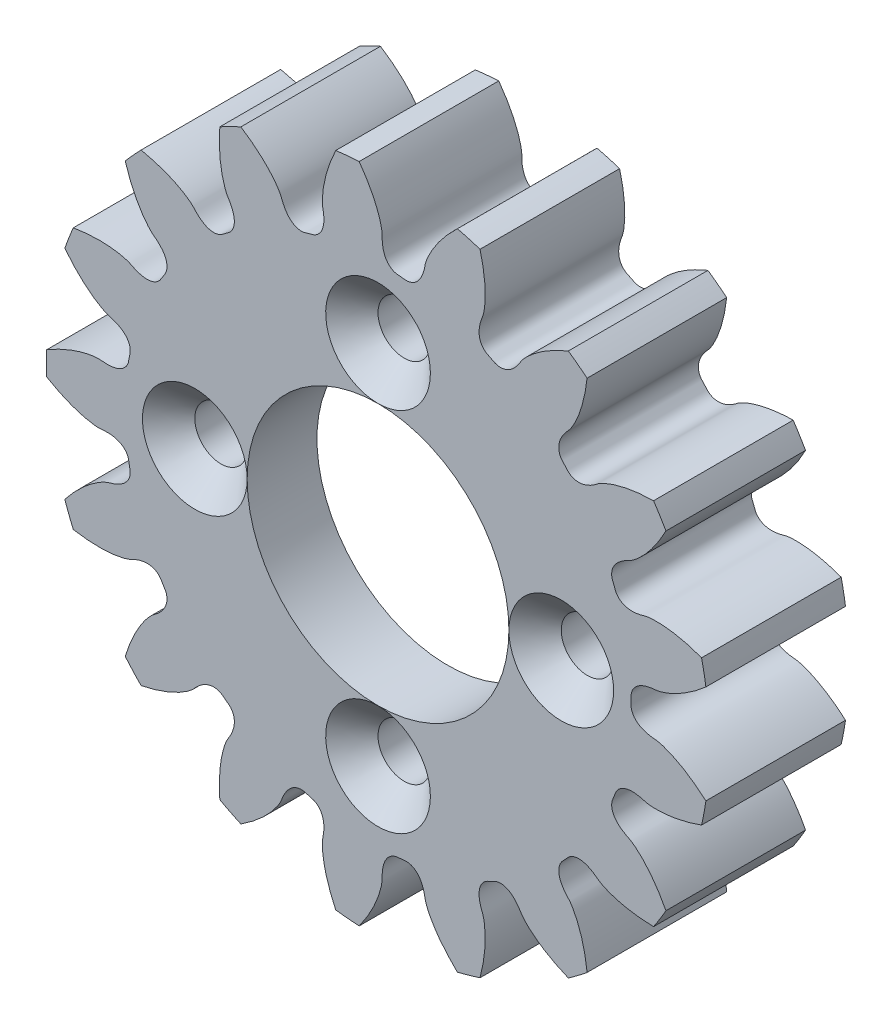
SolidWorks part; units mm, degrees
material "POM 乙缩醛共聚物"
ref_plane "前视基准面" through (0, 0, 0) normal (0, 0, 1) x (1, 0, 0)
ref_plane "上视基准面" through (0, 0, 0) normal (0, 1, 0) x (1, 0, 0)
ref_plane "右视基准面" through (0, 0, 0) normal (1, 0, 0) x (0, 0, -1)
ref_axis "基准轴1" through (0, 0, 55) along (0, 0, -1)
sketch "旋转草图小直齿轮" plane through (0, 0, 0) normal (1, 0, 0) x (0, 0, -1)
  line L0 (0, 0) -> (1, 0) construction
  line L1 (-3, 0) -> (-3, 19)
  line L2 (-3, 19) -> (3, 19)
  line L3 (3, 19) -> (3, 0)
  line L4 (3, 0) -> (-3, 0)
revolve "小直齿轮" add sketch "旋转草图小直齿轮" angle 360 about L0
sketch "齿草图小直齿轮" plane through (0, 0, 0) normal (0, 0, 1) x (1, 0, 0)
  arc A0 (18.8777, 2.9059) -> (18.8777, -2.9059) centre (0, 0) cw
  spline S0 degree 3 number of poles 107 (18.8777, -2.9059) -> (18.8777, 2.9059)
extrude "齿拉伸切除小直齿轮" cut sketch "齿草图小直齿轮" against normal blind 3 and the other way blind 3
pattern_circular "齿形小直齿轮" count 17 every 21.176 about axis through (0, 0, 55) along (0, 0, -1) of "齿拉伸切除小直齿轮"
sketch "孔旋转草图" plane through (0, 0, 0) normal (1, 0, 0) x (0, 0, -1)
  line L0 (0, 0) -> (1, 0) construction
  line L1 (-3, 0) -> (3, 0)
  line L2 (3, 0) -> (3, 5)
  line L3 (3, 5) -> (-3, 5)
  line L4 (-3, 5) -> (-3, 0)
  dimension "TaperSide1" = 5
  dimension "TaperSide2" = 5
revolve "孔旋转切除" cut sketch "孔旋转草图" angle 360 about L0
sketch "辅助草图小直齿轮" plane through (0, 0, 0) normal (0, 0, 1) x (1, 0, 0)
  circle A0 centre (0, 0) radius 17 construction
  circle A1 centre (0, 0) radius 15.9748 construction
  circle A2 centre (0, 0) radius 15.9784 construction
  circle A3 centre (0, 0) radius 19 construction
  circle A4 centre (0, 0) radius 14.5 construction
  dimension "PitchDiameter" = 34
  dimension "BaseDiameter" = 31.9495
  dimension "FormDiameter" = 31.9568
  dimension "MajorDiameter" = 38
  dimension "MinorDiameter" = 29
sketch "草图1" plane through (0, 0, 3) normal (0, 0, 1) x (1, 0, 0)
  circle A0 centre (0, 0) radius 7.5
  circle A1 centre (0, 0) radius 10.5 construction
  circle A2 centre (0, 10.5) radius 1.5
  circle A3 centre (10.5, 0) radius 1.5
  circle A4 centre (0, -10.5) radius 1.5
  circle A5 centre (-10.5, 0) radius 1.5
  point P15 (0, 0)
  dimension "D1" = 15
  dimension "D2" = 21
  dimension "D3" = 3
  dimension "D4" = 4
extrude "切除-拉伸1" cut sketch "草图1" against normal through all
sketch "草图2" plane through (0, 0, -3) normal (0, 0, 1) x (1, 0, 0)
  circle A0 centre (0, 0) radius 13.5
  arc A17 (10.905, -15.5589) -> (11.9807, -14.7466) centre (0, 0) ccw
  arc A18 (15.7892, -10.5689) -> (16.4987, -9.4229) centre (0, 0) ccw
  arc A19 (18.5409, -4.1515) -> (18.7886, -2.8266) centre (0, 0) ccw
  arc A20 (18.7886, 2.8266) -> (18.5409, 4.1515) centre (0, 0) ccw
  arc A21 (16.4987, 9.4229) -> (15.7892, 10.5689) centre (0, 0) ccw
  arc A22 (11.9807, 14.7466) -> (10.905, 15.5589) centre (0, 0) ccw
  arc A23 (5.8445, 18.0788) -> (4.5481, 18.4476) centre (0, 0) ccw
  arc A24 (-1.0809, 18.9692) -> (-2.4231, 18.8449) centre (0, 0) ccw
  arc A25 (-7.8604, 17.2978) -> (-9.067, 16.697) centre (0, 0) ccw
  arc A26 (-13.5783, 13.2902) -> (-14.4864, 12.2941) centre (0, 0) ccw
  arc A27 (-17.4624, 7.4877) -> (-17.9493, 6.2308) centre (0, 0) ccw
  arc A28 (-18.988, 0.6739) -> (-18.988, -0.6739) centre (0, 0) ccw
  arc A29 (-17.9493, -6.2308) -> (-17.4624, -7.4877) centre (0, 0) ccw
  arc A30 (-14.4864, -12.2941) -> (-13.5783, -13.2902) centre (0, 0) ccw
  arc A31 (-9.067, -16.697) -> (-7.8604, -17.2978) centre (0, 0) ccw
  arc A32 (-2.4231, -18.8449) -> (-1.0809, -18.9692) centre (0, 0) ccw
  arc A33 (4.5481, -18.4476) -> (5.8445, -18.0788) centre (0, 0) ccw
  arc A34 (10.905, -15.5589) -> (11.9807, -14.7466) centre (0, 0) ccw
  arc A35 (15.7892, -10.5689) -> (16.4987, -9.4229) centre (0, 0) ccw
  arc A36 (18.5409, -4.1515) -> (18.7886, -2.8266) centre (0, 0) ccw
  arc A37 (18.7886, 2.8266) -> (18.5409, 4.1515) centre (0, 0) ccw
  arc A38 (16.4987, 9.4229) -> (15.7892, 10.5689) centre (0, 0) ccw
  arc A39 (11.9807, 14.7466) -> (10.905, 15.5589) centre (0, 0) ccw
  arc A40 (5.8445, 18.0788) -> (4.5481, 18.4476) centre (0, 0) ccw
  arc A41 (-1.0809, 18.9692) -> (-2.4231, 18.8449) centre (0, 0) ccw
  arc A42 (-7.8604, 17.2978) -> (-9.067, 16.697) centre (0, 0) ccw
  arc A43 (-13.5783, 13.2902) -> (-14.4864, 12.2941) centre (0, 0) ccw
  arc A44 (-17.4624, 7.4877) -> (-17.9493, 6.2308) centre (0, 0) ccw
  arc A45 (-18.988, 0.6739) -> (-18.988, -0.6739) centre (0, 0) ccw
  arc A46 (-17.9493, -6.2308) -> (-17.4624, -7.4877) centre (0, 0) ccw
  arc A47 (-14.4864, -12.2941) -> (-13.5783, -13.2902) centre (0, 0) ccw
  arc A48 (-9.067, -16.697) -> (-7.8604, -17.2978) centre (0, 0) ccw
  arc A49 (-2.4231, -18.8449) -> (-1.0809, -18.9692) centre (0, 0) ccw
  arc A50 (4.5481, -18.4476) -> (5.8445, -18.0788) centre (0, 0) ccw
  spline S17 degree 3 number of poles 107 (5.8445, -18.0788) -> (10.905, -15.5589)
  spline S18 degree 3 number of poles 107 (11.9807, -14.7466) -> (15.7892, -10.5689)
  spline S19 degree 3 number of poles 107 (16.4987, -9.4229) -> (18.5409, -4.1515)
  spline S20 degree 3 number of poles 107 (18.7886, -2.8266) -> (18.7886, 2.8266)
  spline S21 degree 3 number of poles 107 (18.5409, 4.1515) -> (16.4987, 9.4229)
  spline S22 degree 3 number of poles 107 (15.7892, 10.5689) -> (11.9807, 14.7466)
  spline S23 degree 3 number of poles 107 (10.905, 15.5589) -> (5.8445, 18.0788)
  spline S24 degree 3 number of poles 107 (4.5481, 18.4476) -> (-1.0809, 18.9692)
  spline S25 degree 3 number of poles 107 (-2.4231, 18.8449) -> (-7.8604, 17.2978)
  spline S26 degree 3 number of poles 107 (-9.067, 16.697) -> (-13.5783, 13.2902)
  spline S27 degree 3 number of poles 107 (-14.4864, 12.2941) -> (-17.4624, 7.4877)
  spline S28 degree 3 number of poles 107 (-17.9493, 6.2308) -> (-18.988, 0.6739)
  spline S29 degree 3 number of poles 107 (-18.988, -0.6739) -> (-17.9493, -6.2308)
  spline S30 degree 3 number of poles 107 (-17.4624, -7.4877) -> (-14.4864, -12.2941)
  spline S31 degree 3 number of poles 107 (-13.5783, -13.2902) -> (-9.067, -16.697)
  spline S32 degree 3 number of poles 107 (-7.8604, -17.2978) -> (-2.4231, -18.8449)
  spline S33 degree 3 number of poles 107 (-1.0809, -18.9692) -> (4.5481, -18.4476)
  spline S34 degree 3 number of poles 107 (5.8445, -18.0788) -> (10.905, -15.5589)
  spline S35 degree 3 number of poles 107 (11.9807, -14.7466) -> (15.7892, -10.5689)
  spline S36 degree 3 number of poles 107 (16.4987, -9.4229) -> (18.5409, -4.1515)
  spline S37 degree 3 number of poles 107 (18.7886, -2.8266) -> (18.7886, 2.8266)
  spline S38 degree 3 number of poles 107 (18.5409, 4.1515) -> (16.4987, 9.4229)
  spline S39 degree 3 number of poles 107 (15.7892, 10.5689) -> (11.9807, 14.7466)
  spline S40 degree 3 number of poles 107 (10.905, 15.5589) -> (5.8445, 18.0788)
  spline S41 degree 3 number of poles 107 (4.5481, 18.4476) -> (-1.0809, 18.9692)
  spline S42 degree 3 number of poles 107 (-2.4231, 18.8449) -> (-7.8604, 17.2978)
  spline S43 degree 3 number of poles 107 (-9.067, 16.697) -> (-13.5783, 13.2902)
  spline S44 degree 3 number of poles 107 (-14.4864, 12.2941) -> (-17.4624, 7.4877)
  spline S45 degree 3 number of poles 107 (-17.9493, 6.2308) -> (-18.988, 0.6739)
  spline S46 degree 3 number of poles 107 (-18.988, -0.6739) -> (-17.9493, -6.2308)
  spline S47 degree 3 number of poles 107 (-17.4624, -7.4877) -> (-14.4864, -12.2941)
  spline S48 degree 3 number of poles 107 (-13.5783, -13.2902) -> (-9.067, -16.697)
  spline S49 degree 3 number of poles 107 (-7.8604, -17.2978) -> (-2.4231, -18.8449)
  spline S50 degree 3 number of poles 107 (-1.0809, -18.9692) -> (4.5481, -18.4476)
  spline M80 degree 3 poles (5.8133, -18.1938) (5.8714, -17.9845) (5.9469, -17.676) (6.0244, -17.2716) (6.0686, -16.992) (6.1015, -16.7281) (6.1241, -16.4804) (6.1377, -16.2491) (6.1432, -16.0348) (6.1418, -15.8375) (6.1347, -15.6575) (6.1229, -15.4949) (6.1076, -15.3499) (6.09, -15.2224) (6.0711, -15.1125) (6.0521, -15.0201) (6.0341, -14.945) (6.0182, -14.8871) (5.9882, -14.7895) (5.9457, -14.698) (5.9112, -14.5993) (5.8939, -14.5474) (5.878, -14.4959) (5.8633, -14.4449) (5.85, -14.3942) (5.8379, -14.3439) (5.8272, -14.294) (5.8178, -14.2443) (5.8097, -14.195) (5.803, -14.146) (5.7977, -14.0971) (5.7938, -14.0484) (5.7915, -13.9998) (5.7906, -13.9513) (5.7914, -13.9028) (5.7939, -13.8542) (5.7983, -13.8054) (5.8046, -13.7564) (5.8131, -13.7072) (5.8239, -13.6577) (5.8373, -13.6079) (5.8535, -13.5577) (5.8729, -13.5074) (5.8957, -13.4568) (5.9223, -13.4064) (5.953, -13.3563) (5.9881, -13.307) (6.0278, -13.259) (6.0723, -13.2129) (6.1214, -13.1695) (6.175, -13.1294) (6.228, -13.0966) (6.3239, -13.0461) (6.4642, -12.9819) (6.6, -12.9086) (6.6981, -12.8625) (6.7562, -12.84) (6.8205, -12.8214) (6.8847, -12.8083) (6.9483, -12.8006) (7.0106, -12.7978) (7.0711, -12.7995) (7.1296, -12.8052) (7.1858, -12.8144) (7.2399, -12.8266) (7.2918, -12.8416) (7.3416, -12.8588) (7.3894, -12.8782) (7.4354, -12.8994) (7.4798, -12.9223) (7.5227, -12.9467) (7.5642, -12.9727) (7.6045, -12.9999) (7.6437, -13.0286) (7.682, -13.0585) (7.7193, -13.0897) (7.7558, -13.1221) (7.7916, -13.1557) (7.8267, -13.1907) (7.8612, -13.2268) (7.8952, -13.2642) (7.9285, -13.3029) (7.9614, -13.3428) (7.9938, -13.384) (8.0257, -13.4265) (8.0572, -13.4702) (8.0882, -13.5153) (8.1462, -13.6023) (8.1935, -13.6914) (8.2534, -13.7741) (8.29, -13.8217) (8.3391, -13.8813) (8.4014, -13.9521) (8.4777, -14.0334) (8.5688, -14.1243) (8.6753, -14.2239) (8.7979, -14.3313) (8.9373, -14.4455) (9.0939, -14.5655) (9.2683, -14.6903) (9.461, -14.8188) (9.6724, -14.95) (9.9028, -15.0828) (10.1525, -15.2161) (10.522, -15.3979) (10.8136, -15.5236) (11.0157, -15.6033) knots 0 0 0 0 0.058344 0.085213 0.110547 0.134345 0.156608 0.177336 0.196528 0.214185 0.230306 0.244893 0.257943 0.269459 0.279439 0.287883 0.294792 0.300166 0.304005 0.32219 0.327162 0.332059 0.336883 0.341638 0.346326 0.350953 0.355523 0.36004 0.36451 0.36894 0.373335 0.377703 0.382053 0.386393 0.390734 0.395086 0.399462 0.403875 0.408338 0.412867 0.417479 0.422188 0.427012 0.431965 0.437063 0.442315 0.447728 0.453304 0.459035 0.464908 0.470898 0.476975 0.481621 0.5 0.518379 0.523025 0.529102 0.535092 0.540965 0.546696 0.552272 0.557685 0.562937 0.568035 0.572988 0.577812 0.582521 0.587133 0.591662 0.596125 0.600538 0.604914 0.609266 0.613607 0.617947 0.622297 0.626665 0.63106 0.63549 0.63996 0.644477 0.649047 0.653674 0.658362 0.663117 0.667941 0.672838 0.67781 0.695995 0.699834 0.705208 0.712117 0.720561 0.730541 0.742057 0.755107 0.769694 0.785815 0.803472 0.822664 0.843392 0.865655 0.889453 0.914787 0.941656 1 1 1 1 only from (10.905, -15.5589) to (5.8445, -18.0788)
  arc M81 (5.8445, -18.0788) -> (4.5481, -18.4476) centre (0, 0) cw
  spline M82 degree 3 poles (-1.1516, -19.0652) (-1.0218, -18.891) (-0.84, -18.6307) (-0.6216, -18.2816) (-0.4794, -18.0368) (-0.3534, -17.8026) (-0.2428, -17.5798) (-0.1467, -17.3691) (-0.0641, -17.1711) (0.0059, -16.9867) (0.0643, -16.8162) (0.112, -16.6604) (0.1502, -16.5196) (0.1798, -16.3944) (0.2018, -16.2851) (0.2175, -16.192) (0.2279, -16.1155) (0.2339, -16.0558) (0.2413, -15.954) (0.2346, -15.8533) (0.2382, -15.7489) (0.2408, -15.6942) (0.2445, -15.6404) (0.2493, -15.5875) (0.2551, -15.5354) (0.2621, -15.4842) (0.2701, -15.4337) (0.2793, -15.3841) (0.2896, -15.3352) (0.301, -15.287) (0.3137, -15.2395) (0.3277, -15.1927) (0.3431, -15.1466) (0.3598, -15.101) (0.3781, -15.0561) (0.398, -15.0116) (0.4197, -14.9677) (0.4433, -14.9244) (0.4689, -14.8815) (0.4969, -14.8393) (0.5274, -14.7976) (0.5606, -14.7568) (0.5969, -14.7168) (0.6364, -14.6779) (0.6794, -14.6404) (0.7261, -14.6048) (0.7767, -14.5715) (0.8311, -14.5411) (0.8892, -14.5142) (0.9507, -14.4915) (1.0152, -14.4735) (1.0764, -14.462) (1.1841, -14.4496) (1.3381, -14.4404) (1.4912, -14.4211) (1.5993, -14.4136) (1.6616, -14.4136) (1.7283, -14.4194) (1.7929, -14.4305) (1.855, -14.4462) (1.9141, -14.4661) (1.9699, -14.4896) (2.0223, -14.516) (2.0715, -14.5449) (2.1175, -14.5758) (2.1605, -14.6085) (2.2007, -14.6426) (2.2383, -14.6779) (2.2735, -14.7143) (2.3066, -14.7517) (2.3378, -14.79) (2.3672, -14.8292) (2.3949, -14.8692) (2.4211, -14.91) (2.446, -14.9517) (2.4695, -14.9943) (2.4919, -15.0377) (2.5131, -15.082) (2.5332, -15.1273) (2.5523, -15.1734) (2.5704, -15.2206) (2.5876, -15.2687) (2.6038, -15.3178) (2.6192, -15.3679) (2.6336, -15.419) (2.6471, -15.4712) (2.6597, -15.5245) (2.6824, -15.6265) (2.6944, -15.7267) (2.7203, -15.8254) (2.7372, -15.883) (2.7615, -15.9563) (2.794, -16.0449) (2.8358, -16.1483) (2.8879, -16.266) (2.9512, -16.3973) (3.0268, -16.5417) (3.1155, -16.6985) (3.2182, -16.867) (3.3357, -17.0464) (3.469, -17.2358) (3.6186, -17.4345) (3.7855, -17.6416) (3.9703, -17.8561) (4.2491, -18.1591) (4.4756, -18.3816) (4.6353, -18.529) knots 0 0 0 0 0.058344 0.085213 0.110547 0.134345 0.156608 0.177336 0.196528 0.214185 0.230306 0.244893 0.257943 0.269459 0.279439 0.287883 0.294792 0.300166 0.304005 0.32219 0.327162 0.332059 0.336883 0.341638 0.346326 0.350953 0.355523 0.36004 0.36451 0.36894 0.373335 0.377703 0.382053 0.386393 0.390734 0.395086 0.399462 0.403875 0.408338 0.412867 0.417479 0.422188 0.427012 0.431965 0.437063 0.442315 0.447728 0.453304 0.459035 0.464908 0.470898 0.476975 0.481621 0.5 0.518379 0.523025 0.529102 0.535092 0.540965 0.546696 0.552272 0.557685 0.562937 0.568035 0.572988 0.577812 0.582521 0.587133 0.591662 0.596125 0.600538 0.604914 0.609266 0.613607 0.617947 0.622297 0.626665 0.63106 0.63549 0.63996 0.644477 0.649047 0.653674 0.658362 0.663117 0.667941 0.672838 0.67781 0.695995 0.699834 0.705208 0.712117 0.720561 0.730541 0.742057 0.755107 0.769694 0.785815 0.803472 0.822664 0.843392 0.865655 0.889453 0.914787 0.941656 1 1 1 1 only from (4.5481, -18.4476) to (-1.0809, -18.9692)
  arc M83 (-1.0809, -18.9692) -> (-2.4231, -18.8449) centre (0, 0) cw
  spline M84 degree 3 poles (-7.961, -17.3618) (-7.777, -17.2462) (-7.5135, -17.0691) (-7.1837, -16.8225) (-6.9627, -16.6456) (-6.7606, -16.4728) (-6.577, -16.3049) (-6.4112, -16.1432) (-6.2627, -15.9885) (-6.1308, -15.8417) (-6.0148, -15.7039) (-5.914, -15.5758) (-5.8275, -15.4584) (-5.7547, -15.3523) (-5.6946, -15.2583) (-5.6464, -15.1772) (-5.6091, -15.1096) (-5.5819, -15.0561) (-5.5382, -14.9638) (-5.5081, -14.8675) (-5.467, -14.7714) (-5.4449, -14.7214) (-5.422, -14.6726) (-5.3984, -14.625) (-5.3741, -14.5785) (-5.3492, -14.5332) (-5.3234, -14.4891) (-5.297, -14.4461) (-5.2697, -14.4042) (-5.2416, -14.3635) (-5.2126, -14.3238) (-5.1827, -14.2852) (-5.1517, -14.2477) (-5.1196, -14.2113) (-5.0863, -14.1759) (-5.0517, -14.1417) (-5.0156, -14.1086) (-4.978, -14.0767) (-4.9386, -14.046) (-4.8972, -14.0167) (-4.8538, -13.9889) (-4.808, -13.9628) (-4.7597, -13.9386) (-4.7089, -13.9166) (-4.6552, -13.8972) (-4.5988, -13.8809) (-4.5396, -13.8681) (-4.4779, -13.8594) (-4.414, -13.8553) (-4.3484, -13.8563) (-4.2818, -13.8629) (-4.2206, -13.8743) (-4.1156, -13.9016) (-3.9687, -13.9486) (-3.819, -13.986) (-3.7155, -14.018) (-3.6574, -14.0405) (-3.5973, -14.07) (-3.541, -14.1037) (-3.4888, -14.1408) (-3.441, -14.1807) (-3.3974, -14.2227) (-3.358, -14.2663) (-3.3226, -14.311) (-3.2909, -14.3565) (-3.2626, -14.4025) (-3.2375, -14.4488) (-3.2151, -14.4953) (-3.1954, -14.542) (-3.178, -14.5888) (-3.1628, -14.6358) (-3.1496, -14.6829) (-3.1382, -14.7302) (-3.1285, -14.7778) (-3.1204, -14.8256) (-3.1138, -14.8738) (-3.1087, -14.9224) (-3.1049, -14.9714) (-3.1025, -15.0209) (-3.1013, -15.0708) (-3.1014, -15.1213) (-3.1028, -15.1724) (-3.1054, -15.224) (-3.1092, -15.2763) (-3.1143, -15.3292) (-3.1205, -15.3827) (-3.128, -15.4369) (-3.1437, -15.5402) (-3.1687, -15.638) (-3.1802, -15.7394) (-3.1852, -15.7993) (-3.1891, -15.8764) (-3.1908, -15.9707) (-3.1892, -16.0822) (-3.1831, -16.2108) (-3.1715, -16.3561) (-3.1532, -16.5181) (-3.1271, -16.6964) (-3.0922, -16.8905) (-3.0474, -17.1003) (-2.9916, -17.3251) (-2.9238, -17.5644) (-2.843, -17.8178) (-2.7482, -18.0845) (-2.5976, -18.4678) (-2.4668, -18.7571) (-2.3712, -18.9522) knots 0 0 0 0 0.058344 0.085213 0.110547 0.134345 0.156608 0.177336 0.196528 0.214185 0.230306 0.244893 0.257943 0.269459 0.279439 0.287883 0.294792 0.300166 0.304005 0.32219 0.327162 0.332059 0.336883 0.341638 0.346326 0.350953 0.355523 0.36004 0.36451 0.36894 0.373335 0.377703 0.382053 0.386393 0.390734 0.395086 0.399462 0.403875 0.408338 0.412867 0.417479 0.422188 0.427012 0.431965 0.437063 0.442315 0.447728 0.453304 0.459035 0.464908 0.470898 0.476975 0.481621 0.5 0.518379 0.523025 0.529102 0.535092 0.540965 0.546696 0.552272 0.557685 0.562937 0.568035 0.572988 0.577812 0.582521 0.587133 0.591662 0.596125 0.600538 0.604914 0.609266 0.613607 0.617947 0.622297 0.626665 0.63106 0.63549 0.63996 0.644477 0.649047 0.653674 0.658362 0.663117 0.667941 0.672838 0.67781 0.695995 0.699834 0.705208 0.712117 0.720561 0.730541 0.742057 0.755107 0.769694 0.785815 0.803472 0.822664 0.843392 0.865655 0.889453 0.914787 0.941656 1 1 1 1 only from (-2.4231, -18.8449) to (-7.8604, -17.2978)
  arc M85 (-7.8604, -17.2978) -> (-9.067, -16.697) centre (0, 0) cw
  spline M86 degree 3 poles (-13.6953, -13.3135) (-13.4819, -13.2722) (-13.1722, -13.2023) (-12.7756, -13.0915) (-12.5056, -13.0064) (-12.2547, -12.9182) (-12.0229, -12.828) (-11.8098, -12.7371) (-11.6155, -12.6465) (-11.4395, -12.5573) (-11.2815, -12.4707) (-11.1412, -12.3877) (-11.0182, -12.3093) (-10.912, -12.2367) (-10.822, -12.1708) (-10.7478, -12.1126) (-10.6886, -12.063) (-10.6438, -12.023) (-10.5698, -11.9527) (-10.5069, -11.8738) (-10.4339, -11.799) (-10.3952, -11.7604) (-10.3562, -11.7231) (-10.317, -11.6872) (-10.2776, -11.6527) (-10.2379, -11.6195) (-10.198, -11.5876) (-10.1578, -11.5571) (-10.1173, -11.5279) (-10.0763, -11.5) (-10.035, -11.4735) (-9.9931, -11.4484) (-9.9507, -11.4246) (-9.9076, -11.4022) (-9.8638, -11.3813) (-9.8191, -11.3619) (-9.7736, -11.344) (-9.7269, -11.3279) (-9.6791, -11.3135) (-9.6299, -11.3011) (-9.5794, -11.2909) (-9.5273, -11.2831) (-9.4735, -11.2779) (-9.4181, -11.2758) (-9.3611, -11.2771) (-9.3026, -11.2823) (-9.2428, -11.2917) (-9.1821, -11.3059) (-9.121, -11.3252) (-9.0602, -11.3498) (-9.0005, -11.38) (-8.9475, -11.4127) (-8.8596, -11.4761) (-8.7396, -11.573) (-8.6135, -11.6619) (-8.5285, -11.7292) (-8.4824, -11.7712) (-8.4371, -11.8204) (-8.3967, -11.8721) (-8.3615, -11.9256) (-8.3313, -11.9801) (-8.3058, -12.035) (-8.2848, -12.0899) (-8.268, -12.1444) (-8.2548, -12.1982) (-8.2451, -12.2513) (-8.2383, -12.3036) (-8.2343, -12.355) (-8.2328, -12.4057) (-8.2335, -12.4556) (-8.2363, -12.5049) (-8.241, -12.5536) (-8.2474, -12.6019) (-8.2556, -12.6497) (-8.2653, -12.6973) (-8.2766, -12.7446) (-8.2893, -12.7918) (-8.3035, -12.8388) (-8.3191, -12.8858) (-8.3361, -12.9328) (-8.3545, -12.9798) (-8.3742, -13.0269) (-8.3953, -13.0742) (-8.4177, -13.1215) (-8.4415, -13.169) (-8.4666, -13.2167) (-8.4932, -13.2646) (-8.5452, -13.3552) (-8.6038, -13.4373) (-8.6512, -13.5278) (-8.6775, -13.5817) (-8.7089, -13.6523) (-8.7446, -13.7396) (-8.7834, -13.8442) (-8.8242, -13.9662) (-8.8658, -14.106) (-8.9073, -14.2636) (-8.9474, -14.4392) (-8.985, -14.6329) (-9.0189, -14.8447) (-9.0481, -15.0745) (-9.0714, -15.3221) (-9.0875, -15.5876) (-9.0955, -15.8706) (-9.0936, -16.2823) (-9.0761, -16.5994) (-9.0574, -16.8159) knots 0 0 0 0 0.058344 0.085213 0.110547 0.134345 0.156608 0.177336 0.196528 0.214185 0.230306 0.244893 0.257943 0.269459 0.279439 0.287883 0.294792 0.300166 0.304005 0.32219 0.327162 0.332059 0.336883 0.341638 0.346326 0.350953 0.355523 0.36004 0.36451 0.36894 0.373335 0.377703 0.382053 0.386393 0.390734 0.395086 0.399462 0.403875 0.408338 0.412867 0.417479 0.422188 0.427012 0.431965 0.437063 0.442315 0.447728 0.453304 0.459035 0.464908 0.470898 0.476975 0.481621 0.5 0.518379 0.523025 0.529102 0.535092 0.540965 0.546696 0.552272 0.557685 0.562937 0.568035 0.572988 0.577812 0.582521 0.587133 0.591662 0.596125 0.600538 0.604914 0.609266 0.613607 0.617947 0.622297 0.626665 0.63106 0.63549 0.63996 0.644477 0.649047 0.653674 0.658362 0.663117 0.667941 0.672838 0.67781 0.695995 0.699834 0.705208 0.712117 0.720561 0.730541 0.742057 0.755107 0.769694 0.785815 0.803472 0.822664 0.843392 0.865655 0.889453 0.914787 0.941656 1 1 1 1 only from (-9.067, -16.697) to (-13.5783, -13.2902)
  arc M87 (-13.5783, -13.2902) -> (-14.4864, -12.2941) centre (0, 0) cw
  spline M88 degree 3 poles (-17.5798, -7.4672) (-17.366, -7.5058) (-17.0519, -7.5524) (-16.6421, -7.5923) (-16.3596, -7.6105) (-16.0938, -7.6189) (-15.845, -7.6186) (-15.6135, -7.6108) (-15.3995, -7.5965) (-15.2032, -7.5769) (-15.0246, -7.5532) (-14.8638, -7.5265) (-14.7208, -7.4979) (-14.5955, -7.4685) (-14.4879, -7.4396) (-14.3976, -7.4121) (-14.3245, -7.3873) (-14.2683, -7.3661) (-14.1739, -7.3273) (-14.0867, -7.2765) (-13.9916, -7.2331) (-13.9416, -7.211) (-13.8917, -7.1904) (-13.8422, -7.1711) (-13.793, -7.1531) (-13.744, -7.1365) (-13.6953, -7.1212) (-13.6468, -7.1073) (-13.5984, -7.0947) (-13.5502, -7.0835) (-13.502, -7.0737) (-13.4539, -7.0654) (-13.4058, -7.0585) (-13.3575, -7.0532) (-13.3091, -7.0495) (-13.2605, -7.0475) (-13.2115, -7.0474) (-13.1622, -7.0491) (-13.1124, -7.053) (-13.0621, -7.0592) (-13.0112, -7.068) (-12.9598, -7.0795) (-12.9079, -7.0941) (-12.8554, -7.1122) (-12.8028, -7.134) (-12.75, -7.1599) (-12.6977, -7.1903) (-12.6462, -7.2255) (-12.5962, -7.2655) (-12.5485, -7.3104) (-12.5037, -7.3601) (-12.4661, -7.4098) (-12.4069, -7.5007) (-12.3301, -7.6344) (-12.2446, -7.7629) (-12.1896, -7.8563) (-12.1619, -7.9121) (-12.1374, -7.9744) (-12.1184, -8.0372) (-12.1049, -8.0998) (-12.0964, -8.1615) (-12.0925, -8.2219) (-12.0928, -8.2807) (-12.0967, -8.3376) (-12.1039, -8.3925) (-12.114, -8.4455) (-12.1266, -8.4967) (-12.1414, -8.5461) (-12.1583, -8.5939) (-12.177, -8.6402) (-12.1974, -8.6852) (-12.2194, -8.7289) (-12.2428, -8.7716) (-12.2677, -8.8133) (-12.294, -8.8541) (-12.3216, -8.8941) (-12.3505, -8.9335) (-12.3807, -8.9723) (-12.4122, -9.0104) (-12.445, -9.0481) (-12.4792, -9.0854) (-12.5146, -9.1222) (-12.5513, -9.1586) (-12.5893, -9.1946) (-12.6287, -9.2303) (-12.6693, -9.2657) (-12.7114, -9.3007) (-12.7926, -9.3665) (-12.877, -9.4219) (-12.9538, -9.4891) (-12.9978, -9.5299) (-13.0526, -9.5843) (-13.1174, -9.6529) (-13.1913, -9.7364) (-13.2735, -9.8355) (-13.3628, -9.9507) (-13.4584, -10.0827) (-13.5592, -10.232) (-13.6643, -10.3991) (-13.7724, -10.5842) (-13.8826, -10.788) (-13.9938, -11.0105) (-14.1047, -11.2522) (-14.2144, -11.5132) (-14.3614, -11.8978) (-14.4596, -12.1998) (-14.5204, -12.4084) knots 0 0 0 0 0.058344 0.085213 0.110547 0.134345 0.156608 0.177336 0.196528 0.214185 0.230306 0.244893 0.257943 0.269459 0.279439 0.287883 0.294792 0.300166 0.304005 0.32219 0.327162 0.332059 0.336883 0.341638 0.346326 0.350953 0.355523 0.36004 0.36451 0.36894 0.373335 0.377703 0.382053 0.386393 0.390734 0.395086 0.399462 0.403875 0.408338 0.412867 0.417479 0.422188 0.427012 0.431965 0.437063 0.442315 0.447728 0.453304 0.459035 0.464908 0.470898 0.476975 0.481621 0.5 0.518379 0.523025 0.529102 0.535092 0.540965 0.546696 0.552272 0.557685 0.562937 0.568035 0.572988 0.577812 0.582521 0.587133 0.591662 0.596125 0.600538 0.604914 0.609266 0.613607 0.617947 0.622297 0.626665 0.63106 0.63549 0.63996 0.644477 0.649047 0.653674 0.658362 0.663117 0.667941 0.672838 0.67781 0.695995 0.699834 0.705208 0.712117 0.720561 0.730541 0.742057 0.755107 0.769694 0.785815 0.803472 0.822664 0.843392 0.865655 0.889453 0.914787 0.941656 1 1 1 1 only from (-14.4864, -12.2941) to (-17.4624, -7.4877)
  arc M89 (-17.4624, -7.4877) -> (-17.9493, -6.2308) centre (0, 0) cw
  spline M90 degree 3 poles (-19.0902, -0.6124) (-18.9047, -0.7256) (-18.6287, -0.8826) (-18.2609, -1.0678) (-18.0041, -1.1868) (-17.7593, -1.2907) (-17.5272, -1.3803) (-17.3085, -1.4566) (-17.1038, -1.5206) (-16.9137, -1.5732) (-16.7386, -1.6156) (-16.579, -1.6488) (-16.4353, -1.6738) (-16.3079, -1.6917) (-16.197, -1.7036) (-16.1029, -1.7106) (-16.0258, -1.7138) (-15.9657, -1.7144) (-15.8637, -1.7123) (-15.764, -1.6964) (-15.6597, -1.6903) (-15.605, -1.6878) (-15.5511, -1.6866) (-15.498, -1.6865) (-15.4456, -1.6875) (-15.3939, -1.6897) (-15.343, -1.693) (-15.2927, -1.6975) (-15.243, -1.7033) (-15.194, -1.7103) (-15.1456, -1.7185) (-15.0977, -1.7281) (-15.0503, -1.7391) (-15.0034, -1.7516) (-14.9569, -1.7657) (-14.9109, -1.7814) (-14.8652, -1.7989) (-14.8198, -1.8184) (-14.7748, -1.84) (-14.7301, -1.864) (-14.6859, -1.8905) (-14.6421, -1.9198) (-14.5989, -1.9522) (-14.5566, -1.988) (-14.5153, -2.0274) (-14.4755, -2.0706) (-14.4377, -2.1179) (-14.4024, -2.1692) (-14.3702, -2.2246) (-14.3419, -2.2838) (-14.3181, -2.3463) (-14.301, -2.4062) (-14.2787, -2.5123) (-14.2553, -2.6648) (-14.222, -2.8154) (-14.2045, -2.9224) (-14.1988, -2.9845) (-14.1984, -3.0514) (-14.2035, -3.1168) (-14.2134, -3.18) (-14.2278, -3.2407) (-14.246, -3.2984) (-14.2675, -3.3531) (-14.2917, -3.4047) (-14.3183, -3.4533) (-14.3468, -3.4992) (-14.3771, -3.5423) (-14.4088, -3.583) (-14.4418, -3.6215) (-14.4759, -3.6579) (-14.5112, -3.6925) (-14.5475, -3.7253) (-14.5848, -3.7566) (-14.623, -3.7865) (-14.6623, -3.8151) (-14.7025, -3.8425) (-14.7436, -3.8687) (-14.7858, -3.8939) (-14.829, -3.9182) (-14.8732, -3.9415) (-14.9185, -3.9638) (-14.9648, -3.9854) (-15.0122, -4.0061) (-15.0607, -4.0259) (-15.1103, -4.045) (-15.161, -4.0633) (-15.2128, -4.0808) (-15.3123, -4.1128) (-15.411, -4.1339) (-15.5069, -4.1689) (-15.5627, -4.1911) (-15.6334, -4.222) (-15.7187, -4.2625) (-15.8178, -4.3136) (-15.9301, -4.3764) (-16.0551, -4.4516) (-16.1919, -4.5401) (-16.3398, -4.6429) (-16.4981, -4.7607) (-16.6659, -4.8943) (-16.8422, -5.0445) (-17.0263, -5.2119) (-17.217, -5.3971) (-17.4136, -5.6009) (-17.6896, -5.9065) (-17.8902, -6.1526) (-18.0223, -6.3251) knots 0 0 0 0 0.058344 0.085213 0.110547 0.134345 0.156608 0.177336 0.196528 0.214185 0.230306 0.244893 0.257943 0.269459 0.279439 0.287883 0.294792 0.300166 0.304005 0.32219 0.327162 0.332059 0.336883 0.341638 0.346326 0.350953 0.355523 0.36004 0.36451 0.36894 0.373335 0.377703 0.382053 0.386393 0.390734 0.395086 0.399462 0.403875 0.408338 0.412867 0.417479 0.422188 0.427012 0.431965 0.437063 0.442315 0.447728 0.453304 0.459035 0.464908 0.470898 0.476975 0.481621 0.5 0.518379 0.523025 0.529102 0.535092 0.540965 0.546696 0.552272 0.557685 0.562937 0.568035 0.572988 0.577812 0.582521 0.587133 0.591662 0.596125 0.600538 0.604914 0.609266 0.613607 0.617947 0.622297 0.626665 0.63106 0.63549 0.63996 0.644477 0.649047 0.653674 0.658362 0.663117 0.667941 0.672838 0.67781 0.695995 0.699834 0.705208 0.712117 0.720561 0.730541 0.742057 0.755107 0.769694 0.785815 0.803472 0.822664 0.843392 0.865655 0.889453 0.914787 0.941656 1 1 1 1 only from (-17.9493, -6.2308) to (-18.988, -0.6739)
  arc M91 (-18.988, -0.6739) -> (-18.988, 0.6739) centre (0, 0) cw
  spline M92 degree 3 poles (-18.0223, 6.3251) (-17.8902, 6.1526) (-17.6896, 5.9065) (-17.4136, 5.6009) (-17.217, 5.3971) (-17.0263, 5.2119) (-16.8422, 5.0445) (-16.6659, 4.8943) (-16.4981, 4.7607) (-16.3398, 4.6429) (-16.1919, 4.5401) (-16.0551, 4.4516) (-15.9301, 4.3764) (-15.8178, 4.3136) (-15.7187, 4.2625) (-15.6334, 4.222) (-15.5627, 4.1911) (-15.5069, 4.1689) (-15.411, 4.1339) (-15.3123, 4.1128) (-15.2128, 4.0808) (-15.161, 4.0633) (-15.1103, 4.045) (-15.0607, 4.0259) (-15.0122, 4.0061) (-14.9648, 3.9854) (-14.9185, 3.9638) (-14.8732, 3.9415) (-14.829, 3.9182) (-14.7858, 3.8939) (-14.7436, 3.8687) (-14.7025, 3.8425) (-14.6623, 3.8151) (-14.623, 3.7865) (-14.5848, 3.7566) (-14.5475, 3.7253) (-14.5112, 3.6925) (-14.4759, 3.6579) (-14.4418, 3.6215) (-14.4088, 3.583) (-14.3771, 3.5423) (-14.3468, 3.4992) (-14.3183, 3.4533) (-14.2917, 3.4047) (-14.2675, 3.3531) (-14.246, 3.2984) (-14.2278, 3.2407) (-14.2134, 3.18) (-14.2035, 3.1168) (-14.1984, 3.0514) (-14.1988, 2.9845) (-14.2045, 2.9224) (-14.222, 2.8154) (-14.2553, 2.6648) (-14.2787, 2.5123) (-14.301, 2.4062) (-14.3181, 2.3463) (-14.3419, 2.2838) (-14.3702, 2.2246) (-14.4024, 2.1692) (-14.4377, 2.1179) (-14.4755, 2.0706) (-14.5153, 2.0274) (-14.5566, 1.988) (-14.5989, 1.9522) (-14.6421, 1.9198) (-14.6859, 1.8905) (-14.7301, 1.864) (-14.7748, 1.84) (-14.8198, 1.8184) (-14.8652, 1.7989) (-14.9109, 1.7814) (-14.9569, 1.7657) (-15.0034, 1.7516) (-15.0503, 1.7391) (-15.0977, 1.7281) (-15.1456, 1.7185) (-15.194, 1.7103) (-15.243, 1.7033) (-15.2927, 1.6975) (-15.343, 1.693) (-15.3939, 1.6897) (-15.4456, 1.6875) (-15.498, 1.6865) (-15.5511, 1.6866) (-15.605, 1.6878) (-15.6597, 1.6903) (-15.764, 1.6964) (-15.8637, 1.7123) (-15.9657, 1.7144) (-16.0258, 1.7138) (-16.1029, 1.7106) (-16.197, 1.7036) (-16.3079, 1.6917) (-16.4353, 1.6738) (-16.579, 1.6488) (-16.7386, 1.6156) (-16.9137, 1.5732) (-17.1038, 1.5206) (-17.3085, 1.4566) (-17.5272, 1.3803) (-17.7593, 1.2907) (-18.0041, 1.1868) (-18.2609, 1.0678) (-18.6287, 0.8826) (-18.9047, 0.7256) (-19.0902, 0.6124) knots 0 0 0 0 0.058344 0.085213 0.110547 0.134345 0.156608 0.177336 0.196528 0.214185 0.230306 0.244893 0.257943 0.269459 0.279439 0.287883 0.294792 0.300166 0.304005 0.32219 0.327162 0.332059 0.336883 0.341638 0.346326 0.350953 0.355523 0.36004 0.36451 0.36894 0.373335 0.377703 0.382053 0.386393 0.390734 0.395086 0.399462 0.403875 0.408338 0.412867 0.417479 0.422188 0.427012 0.431965 0.437063 0.442315 0.447728 0.453304 0.459035 0.464908 0.470898 0.476975 0.481621 0.5 0.518379 0.523025 0.529102 0.535092 0.540965 0.546696 0.552272 0.557685 0.562937 0.568035 0.572988 0.577812 0.582521 0.587133 0.591662 0.596125 0.600538 0.604914 0.609266 0.613607 0.617947 0.622297 0.626665 0.63106 0.63549 0.63996 0.644477 0.649047 0.653674 0.658362 0.663117 0.667941 0.672838 0.67781 0.695995 0.699834 0.705208 0.712117 0.720561 0.730541 0.742057 0.755107 0.769694 0.785815 0.803472 0.822664 0.843392 0.865655 0.889453 0.914787 0.941656 1 1 1 1 only from (-18.988, 0.6739) to (-17.9493, 6.2308)
  arc M93 (-17.9493, 6.2308) -> (-17.4624, 7.4877) centre (0, 0) cw
  spline M94 degree 3 poles (-14.5204, 12.4084) (-14.4596, 12.1998) (-14.3614, 11.8978) (-14.2144, 11.5132) (-14.1047, 11.2522) (-13.9938, 11.0105) (-13.8826, 10.788) (-13.7724, 10.5842) (-13.6643, 10.3991) (-13.5592, 10.232) (-13.4584, 10.0827) (-13.3628, 9.9507) (-13.2735, 9.8355) (-13.1913, 9.7364) (-13.1174, 9.6529) (-13.0526, 9.5843) (-12.9978, 9.5299) (-12.9538, 9.4891) (-12.877, 9.4219) (-12.7926, 9.3665) (-12.7114, 9.3007) (-12.6693, 9.2657) (-12.6287, 9.2303) (-12.5893, 9.1946) (-12.5513, 9.1586) (-12.5146, 9.1222) (-12.4792, 9.0854) (-12.445, 9.0481) (-12.4122, 9.0104) (-12.3807, 8.9723) (-12.3505, 8.9335) (-12.3216, 8.8941) (-12.294, 8.8541) (-12.2677, 8.8133) (-12.2428, 8.7716) (-12.2194, 8.7289) (-12.1974, 8.6852) (-12.177, 8.6402) (-12.1583, 8.5939) (-12.1414, 8.5461) (-12.1266, 8.4967) (-12.114, 8.4455) (-12.1039, 8.3925) (-12.0967, 8.3376) (-12.0928, 8.2807) (-12.0925, 8.2219) (-12.0964, 8.1615) (-12.1049, 8.0998) (-12.1184, 8.0372) (-12.1374, 7.9744) (-12.1619, 7.9121) (-12.1896, 7.8563) (-12.2446, 7.7629) (-12.3301, 7.6344) (-12.4069, 7.5007) (-12.4661, 7.4098) (-12.5037, 7.3601) (-12.5485, 7.3104) (-12.5962, 7.2655) (-12.6462, 7.2255) (-12.6977, 7.1903) (-12.75, 7.1599) (-12.8028, 7.134) (-12.8554, 7.1122) (-12.9079, 7.0941) (-12.9598, 7.0795) (-13.0112, 7.068) (-13.0621, 7.0592) (-13.1124, 7.053) (-13.1622, 7.0491) (-13.2115, 7.0474) (-13.2605, 7.0475) (-13.3091, 7.0495) (-13.3575, 7.0532) (-13.4058, 7.0585) (-13.4539, 7.0654) (-13.502, 7.0737) (-13.5502, 7.0835) (-13.5984, 7.0947) (-13.6468, 7.1073) (-13.6953, 7.1212) (-13.744, 7.1365) (-13.793, 7.1531) (-13.8422, 7.1711) (-13.8917, 7.1904) (-13.9416, 7.211) (-13.9916, 7.2331) (-14.0867, 7.2765) (-14.1739, 7.3273) (-14.2683, 7.3661) (-14.3245, 7.3873) (-14.3976, 7.4121) (-14.4879, 7.4396) (-14.5955, 7.4685) (-14.7208, 7.4979) (-14.8638, 7.5265) (-15.0246, 7.5532) (-15.2032, 7.5769) (-15.3995, 7.5965) (-15.6135, 7.6108) (-15.845, 7.6186) (-16.0938, 7.6189) (-16.3596, 7.6105) (-16.6421, 7.5923) (-17.0519, 7.5524) (-17.366, 7.5058) (-17.5798, 7.4672) knots 0 0 0 0 0.058344 0.085213 0.110547 0.134345 0.156608 0.177336 0.196528 0.214185 0.230306 0.244893 0.257943 0.269459 0.279439 0.287883 0.294792 0.300166 0.304005 0.32219 0.327162 0.332059 0.336883 0.341638 0.346326 0.350953 0.355523 0.36004 0.36451 0.36894 0.373335 0.377703 0.382053 0.386393 0.390734 0.395086 0.399462 0.403875 0.408338 0.412867 0.417479 0.422188 0.427012 0.431965 0.437063 0.442315 0.447728 0.453304 0.459035 0.464908 0.470898 0.476975 0.481621 0.5 0.518379 0.523025 0.529102 0.535092 0.540965 0.546696 0.552272 0.557685 0.562937 0.568035 0.572988 0.577812 0.582521 0.587133 0.591662 0.596125 0.600538 0.604914 0.609266 0.613607 0.617947 0.622297 0.626665 0.63106 0.63549 0.63996 0.644477 0.649047 0.653674 0.658362 0.663117 0.667941 0.672838 0.67781 0.695995 0.699834 0.705208 0.712117 0.720561 0.730541 0.742057 0.755107 0.769694 0.785815 0.803472 0.822664 0.843392 0.865655 0.889453 0.914787 0.941656 1 1 1 1 only from (-17.4624, 7.4877) to (-14.4864, 12.2941)
  arc M95 (-14.4864, 12.2941) -> (-13.5783, 13.2902) centre (0, 0) cw
  spline M96 degree 3 poles (-9.0574, 16.8159) (-9.0761, 16.5994) (-9.0936, 16.2823) (-9.0955, 15.8706) (-9.0875, 15.5876) (-9.0714, 15.3221) (-9.0481, 15.0745) (-9.0189, 14.8447) (-8.985, 14.6329) (-8.9474, 14.4392) (-8.9073, 14.2636) (-8.8658, 14.106) (-8.8242, 13.9662) (-8.7834, 13.8442) (-8.7446, 13.7396) (-8.7089, 13.6523) (-8.6775, 13.5817) (-8.6512, 13.5278) (-8.6038, 13.4373) (-8.5452, 13.3552) (-8.4932, 13.2646) (-8.4666, 13.2167) (-8.4415, 13.169) (-8.4177, 13.1215) (-8.3953, 13.0742) (-8.3742, 13.0269) (-8.3545, 12.9798) (-8.3361, 12.9328) (-8.3191, 12.8858) (-8.3035, 12.8388) (-8.2893, 12.7918) (-8.2766, 12.7446) (-8.2653, 12.6973) (-8.2556, 12.6497) (-8.2474, 12.6019) (-8.241, 12.5536) (-8.2363, 12.5049) (-8.2335, 12.4556) (-8.2328, 12.4057) (-8.2343, 12.355) (-8.2383, 12.3036) (-8.2451, 12.2513) (-8.2548, 12.1982) (-8.268, 12.1444) (-8.2848, 12.0899) (-8.3058, 12.035) (-8.3313, 11.9801) (-8.3615, 11.9256) (-8.3967, 11.8721) (-8.4371, 11.8204) (-8.4824, 11.7712) (-8.5285, 11.7292) (-8.6135, 11.6619) (-8.7396, 11.573) (-8.8596, 11.4761) (-8.9475, 11.4127) (-9.0005, 11.38) (-9.0602, 11.3498) (-9.121, 11.3252) (-9.1821, 11.3059) (-9.2428, 11.2917) (-9.3026, 11.2823) (-9.3611, 11.2771) (-9.4181, 11.2758) (-9.4735, 11.2779) (-9.5273, 11.2831) (-9.5794, 11.2909) (-9.6299, 11.3011) (-9.6791, 11.3135) (-9.7269, 11.3279) (-9.7736, 11.344) (-9.8191, 11.3619) (-9.8638, 11.3813) (-9.9076, 11.4022) (-9.9507, 11.4246) (-9.9931, 11.4484) (-10.035, 11.4735) (-10.0763, 11.5) (-10.1173, 11.5279) (-10.1578, 11.5571) (-10.198, 11.5876) (-10.2379, 11.6195) (-10.2776, 11.6527) (-10.317, 11.6872) (-10.3562, 11.7231) (-10.3952, 11.7604) (-10.4339, 11.799) (-10.5069, 11.8738) (-10.5698, 11.9527) (-10.6438, 12.023) (-10.6886, 12.063) (-10.7478, 12.1126) (-10.822, 12.1708) (-10.912, 12.2367) (-11.0182, 12.3093) (-11.1412, 12.3877) (-11.2815, 12.4707) (-11.4395, 12.5573) (-11.6155, 12.6465) (-11.8098, 12.7371) (-12.0229, 12.828) (-12.2547, 12.9182) (-12.5056, 13.0064) (-12.7756, 13.0915) (-13.1722, 13.2023) (-13.4819, 13.2722) (-13.6953, 13.3135) knots 0 0 0 0 0.058344 0.085213 0.110547 0.134345 0.156608 0.177336 0.196528 0.214185 0.230306 0.244893 0.257943 0.269459 0.279439 0.287883 0.294792 0.300166 0.304005 0.32219 0.327162 0.332059 0.336883 0.341638 0.346326 0.350953 0.355523 0.36004 0.36451 0.36894 0.373335 0.377703 0.382053 0.386393 0.390734 0.395086 0.399462 0.403875 0.408338 0.412867 0.417479 0.422188 0.427012 0.431965 0.437063 0.442315 0.447728 0.453304 0.459035 0.464908 0.470898 0.476975 0.481621 0.5 0.518379 0.523025 0.529102 0.535092 0.540965 0.546696 0.552272 0.557685 0.562937 0.568035 0.572988 0.577812 0.582521 0.587133 0.591662 0.596125 0.600538 0.604914 0.609266 0.613607 0.617947 0.622297 0.626665 0.63106 0.63549 0.63996 0.644477 0.649047 0.653674 0.658362 0.663117 0.667941 0.672838 0.67781 0.695995 0.699834 0.705208 0.712117 0.720561 0.730541 0.742057 0.755107 0.769694 0.785815 0.803472 0.822664 0.843392 0.865655 0.889453 0.914787 0.941656 1 1 1 1 only from (-13.5783, 13.2902) to (-9.067, 16.697)
  arc M97 (-9.067, 16.697) -> (-7.8604, 17.2978) centre (0, 0) cw
  spline M98 degree 3 poles (-2.3712, 18.9522) (-2.4668, 18.7571) (-2.5976, 18.4678) (-2.7482, 18.0845) (-2.843, 17.8178) (-2.9238, 17.5644) (-2.9916, 17.3251) (-3.0474, 17.1003) (-3.0922, 16.8905) (-3.1271, 16.6964) (-3.1532, 16.5181) (-3.1715, 16.3561) (-3.1831, 16.2108) (-3.1892, 16.0822) (-3.1908, 15.9707) (-3.1891, 15.8764) (-3.1852, 15.7993) (-3.1802, 15.7394) (-3.1687, 15.638) (-3.1437, 15.5402) (-3.128, 15.4369) (-3.1205, 15.3827) (-3.1143, 15.3292) (-3.1092, 15.2763) (-3.1054, 15.224) (-3.1028, 15.1724) (-3.1014, 15.1213) (-3.1013, 15.0708) (-3.1025, 15.0209) (-3.1049, 14.9714) (-3.1087, 14.9224) (-3.1138, 14.8738) (-3.1204, 14.8256) (-3.1285, 14.7778) (-3.1382, 14.7302) (-3.1496, 14.6829) (-3.1628, 14.6358) (-3.178, 14.5888) (-3.1954, 14.542) (-3.2151, 14.4953) (-3.2375, 14.4488) (-3.2626, 14.4025) (-3.2909, 14.3565) (-3.3226, 14.311) (-3.358, 14.2663) (-3.3974, 14.2227) (-3.441, 14.1807) (-3.4888, 14.1408) (-3.541, 14.1037) (-3.5973, 14.07) (-3.6574, 14.0405) (-3.7155, 14.018) (-3.819, 13.986) (-3.9687, 13.9486) (-4.1156, 13.9016) (-4.2206, 13.8743) (-4.2818, 13.8629) (-4.3484, 13.8563) (-4.414, 13.8553) (-4.4779, 13.8594) (-4.5396, 13.8681) (-4.5988, 13.8809) (-4.6552, 13.8972) (-4.7089, 13.9166) (-4.7597, 13.9386) (-4.808, 13.9628) (-4.8538, 13.9889) (-4.8972, 14.0167) (-4.9386, 14.046) (-4.978, 14.0767) (-5.0156, 14.1086) (-5.0517, 14.1417) (-5.0863, 14.1759) (-5.1196, 14.2113) (-5.1517, 14.2477) (-5.1827, 14.2852) (-5.2126, 14.3238) (-5.2416, 14.3635) (-5.2697, 14.4042) (-5.297, 14.4461) (-5.3234, 14.4891) (-5.3492, 14.5332) (-5.3741, 14.5785) (-5.3984, 14.625) (-5.422, 14.6726) (-5.4449, 14.7214) (-5.467, 14.7714) (-5.5081, 14.8675) (-5.5382, 14.9638) (-5.5819, 15.0561) (-5.6091, 15.1096) (-5.6464, 15.1772) (-5.6946, 15.2583) (-5.7547, 15.3523) (-5.8275, 15.4584) (-5.914, 15.5758) (-6.0148, 15.7039) (-6.1308, 15.8417) (-6.2627, 15.9885) (-6.4112, 16.1432) (-6.577, 16.3049) (-6.7606, 16.4728) (-6.9627, 16.6456) (-7.1837, 16.8225) (-7.5135, 17.0691) (-7.777, 17.2462) (-7.961, 17.3618) knots 0 0 0 0 0.058344 0.085213 0.110547 0.134345 0.156608 0.177336 0.196528 0.214185 0.230306 0.244893 0.257943 0.269459 0.279439 0.287883 0.294792 0.300166 0.304005 0.32219 0.327162 0.332059 0.336883 0.341638 0.346326 0.350953 0.355523 0.36004 0.36451 0.36894 0.373335 0.377703 0.382053 0.386393 0.390734 0.395086 0.399462 0.403875 0.408338 0.412867 0.417479 0.422188 0.427012 0.431965 0.437063 0.442315 0.447728 0.453304 0.459035 0.464908 0.470898 0.476975 0.481621 0.5 0.518379 0.523025 0.529102 0.535092 0.540965 0.546696 0.552272 0.557685 0.562937 0.568035 0.572988 0.577812 0.582521 0.587133 0.591662 0.596125 0.600538 0.604914 0.609266 0.613607 0.617947 0.622297 0.626665 0.63106 0.63549 0.63996 0.644477 0.649047 0.653674 0.658362 0.663117 0.667941 0.672838 0.67781 0.695995 0.699834 0.705208 0.712117 0.720561 0.730541 0.742057 0.755107 0.769694 0.785815 0.803472 0.822664 0.843392 0.865655 0.889453 0.914787 0.941656 1 1 1 1 only from (-7.8604, 17.2978) to (-2.4231, 18.8449)
  arc M99 (-2.4231, 18.8449) -> (-1.0809, 18.9692) centre (0, 0) cw
  spline M100 degree 3 poles (4.6353, 18.529) (4.4756, 18.3816) (4.2491, 18.1591) (3.9703, 17.8561) (3.7855, 17.6416) (3.6186, 17.4345) (3.469, 17.2358) (3.3357, 17.0464) (3.2182, 16.867) (3.1155, 16.6985) (3.0268, 16.5417) (2.9512, 16.3973) (2.8879, 16.266) (2.8358, 16.1483) (2.794, 16.0449) (2.7615, 15.9563) (2.7372, 15.883) (2.7203, 15.8254) (2.6944, 15.7267) (2.6824, 15.6265) (2.6597, 15.5245) (2.6471, 15.4712) (2.6336, 15.419) (2.6192, 15.3679) (2.6038, 15.3178) (2.5876, 15.2687) (2.5704, 15.2206) (2.5523, 15.1734) (2.5332, 15.1273) (2.5131, 15.082) (2.4919, 15.0377) (2.4695, 14.9943) (2.446, 14.9517) (2.4211, 14.91) (2.3949, 14.8692) (2.3672, 14.8292) (2.3378, 14.79) (2.3066, 14.7517) (2.2735, 14.7143) (2.2383, 14.6779) (2.2007, 14.6426) (2.1605, 14.6085) (2.1175, 14.5758) (2.0715, 14.5449) (2.0223, 14.516) (1.9699, 14.4896) (1.9141, 14.4661) (1.855, 14.4462) (1.7929, 14.4305) (1.7283, 14.4194) (1.6616, 14.4136) (1.5993, 14.4136) (1.4912, 14.4211) (1.3381, 14.4404) (1.1841, 14.4496) (1.0764, 14.462) (1.0152, 14.4735) (0.9507, 14.4915) (0.8892, 14.5142) (0.8311, 14.5411) (0.7767, 14.5715) (0.7261, 14.6048) (0.6794, 14.6404) (0.6364, 14.6779) (0.5969, 14.7168) (0.5606, 14.7568) (0.5274, 14.7976) (0.4969, 14.8393) (0.4689, 14.8815) (0.4433, 14.9244) (0.4197, 14.9677) (0.398, 15.0116) (0.3781, 15.0561) (0.3598, 15.101) (0.3431, 15.1466) (0.3277, 15.1927) (0.3137, 15.2395) (0.301, 15.287) (0.2896, 15.3352) (0.2793, 15.3841) (0.2701, 15.4337) (0.2621, 15.4842) (0.2551, 15.5354) (0.2493, 15.5875) (0.2445, 15.6404) (0.2408, 15.6942) (0.2382, 15.7489) (0.2346, 15.8533) (0.2413, 15.954) (0.2339, 16.0558) (0.2279, 16.1155) (0.2175, 16.192) (0.2018, 16.2851) (0.1798, 16.3944) (0.1502, 16.5196) (0.112, 16.6604) (0.0643, 16.8162) (0.0059, 16.9867) (-0.0641, 17.1711) (-0.1467, 17.3691) (-0.2428, 17.5798) (-0.3534, 17.8026) (-0.4794, 18.0368) (-0.6216, 18.2816) (-0.84, 18.6307) (-1.0218, 18.891) (-1.1516, 19.0652) knots 0 0 0 0 0.058344 0.085213 0.110547 0.134345 0.156608 0.177336 0.196528 0.214185 0.230306 0.244893 0.257943 0.269459 0.279439 0.287883 0.294792 0.300166 0.304005 0.32219 0.327162 0.332059 0.336883 0.341638 0.346326 0.350953 0.355523 0.36004 0.36451 0.36894 0.373335 0.377703 0.382053 0.386393 0.390734 0.395086 0.399462 0.403875 0.408338 0.412867 0.417479 0.422188 0.427012 0.431965 0.437063 0.442315 0.447728 0.453304 0.459035 0.464908 0.470898 0.476975 0.481621 0.5 0.518379 0.523025 0.529102 0.535092 0.540965 0.546696 0.552272 0.557685 0.562937 0.568035 0.572988 0.577812 0.582521 0.587133 0.591662 0.596125 0.600538 0.604914 0.609266 0.613607 0.617947 0.622297 0.626665 0.63106 0.63549 0.63996 0.644477 0.649047 0.653674 0.658362 0.663117 0.667941 0.672838 0.67781 0.695995 0.699834 0.705208 0.712117 0.720561 0.730541 0.742057 0.755107 0.769694 0.785815 0.803472 0.822664 0.843392 0.865655 0.889453 0.914787 0.941656 1 1 1 1 only from (-1.0809, 18.9692) to (4.5481, 18.4476)
  arc M101 (4.5481, 18.4476) -> (5.8445, 18.0788) centre (0, 0) cw
  spline M102 degree 3 poles (11.0157, 15.6033) (10.8136, 15.5236) (10.522, 15.3979) (10.1525, 15.2161) (9.9028, 15.0828) (9.6724, 14.95) (9.461, 14.8188) (9.2683, 14.6903) (9.0939, 14.5655) (8.9373, 14.4455) (8.7979, 14.3313) (8.6753, 14.2239) (8.5688, 14.1243) (8.4777, 14.0334) (8.4014, 13.9521) (8.3391, 13.8813) (8.29, 13.8217) (8.2534, 13.7741) (8.1935, 13.6914) (8.1462, 13.6023) (8.0882, 13.5153) (8.0572, 13.4702) (8.0257, 13.4265) (7.9938, 13.384) (7.9614, 13.3428) (7.9285, 13.3029) (7.8952, 13.2642) (7.8612, 13.2268) (7.8267, 13.1907) (7.7916, 13.1557) (7.7558, 13.1221) (7.7193, 13.0897) (7.682, 13.0585) (7.6437, 13.0286) (7.6045, 12.9999) (7.5642, 12.9727) (7.5227, 12.9467) (7.4798, 12.9223) (7.4354, 12.8994) (7.3894, 12.8782) (7.3416, 12.8588) (7.2918, 12.8416) (7.2399, 12.8266) (7.1858, 12.8144) (7.1296, 12.8052) (7.0711, 12.7995) (7.0106, 12.7978) (6.9483, 12.8006) (6.8847, 12.8083) (6.8205, 12.8214) (6.7562, 12.84) (6.6981, 12.8625) (6.6, 12.9086) (6.4642, 12.9819) (6.3239, 13.0461) (6.228, 13.0966) (6.175, 13.1294) (6.1214, 13.1695) (6.0723, 13.2129) (6.0278, 13.259) (5.9881, 13.307) (5.953, 13.3563) (5.9223, 13.4064) (5.8957, 13.4568) (5.8729, 13.5074) (5.8535, 13.5577) (5.8373, 13.6079) (5.8239, 13.6577) (5.8131, 13.7072) (5.8046, 13.7564) (5.7983, 13.8054) (5.7939, 13.8542) (5.7914, 13.9028) (5.7906, 13.9513) (5.7915, 13.9998) (5.7938, 14.0484) (5.7977, 14.0971) (5.803, 14.146) (5.8097, 14.195) (5.8178, 14.2443) (5.8272, 14.294) (5.8379, 14.3439) (5.85, 14.3942) (5.8633, 14.4449) (5.878, 14.4959) (5.8939, 14.5474) (5.9112, 14.5993) (5.9457, 14.698) (5.9882, 14.7895) (6.0182, 14.8871) (6.0341, 14.945) (6.0521, 15.0201) (6.0711, 15.1125) (6.09, 15.2224) (6.1076, 15.3499) (6.1229, 15.4949) (6.1347, 15.6575) (6.1418, 15.8375) (6.1432, 16.0348) (6.1377, 16.2491) (6.1241, 16.4804) (6.1015, 16.7281) (6.0686, 16.992) (6.0244, 17.2716) (5.9469, 17.676) (5.8714, 17.9845) (5.8133, 18.1938) knots 0 0 0 0 0.058344 0.085213 0.110547 0.134345 0.156608 0.177336 0.196528 0.214185 0.230306 0.244893 0.257943 0.269459 0.279439 0.287883 0.294792 0.300166 0.304005 0.32219 0.327162 0.332059 0.336883 0.341638 0.346326 0.350953 0.355523 0.36004 0.36451 0.36894 0.373335 0.377703 0.382053 0.386393 0.390734 0.395086 0.399462 0.403875 0.408338 0.412867 0.417479 0.422188 0.427012 0.431965 0.437063 0.442315 0.447728 0.453304 0.459035 0.464908 0.470898 0.476975 0.481621 0.5 0.518379 0.523025 0.529102 0.535092 0.540965 0.546696 0.552272 0.557685 0.562937 0.568035 0.572988 0.577812 0.582521 0.587133 0.591662 0.596125 0.600538 0.604914 0.609266 0.613607 0.617947 0.622297 0.626665 0.63106 0.63549 0.63996 0.644477 0.649047 0.653674 0.658362 0.663117 0.667941 0.672838 0.67781 0.695995 0.699834 0.705208 0.712117 0.720561 0.730541 0.742057 0.755107 0.769694 0.785815 0.803472 0.822664 0.843392 0.865655 0.889453 0.914787 0.941656 1 1 1 1 only from (5.8445, 18.0788) to (10.905, 15.5589)
  arc M103 (10.905, 15.5589) -> (11.9807, 14.7466) centre (0, 0) cw
  spline M104 degree 3 poles (15.9084, 10.5703) (15.6911, 10.569) (15.3738, 10.5571) (14.9636, 10.521) (14.6826, 10.487) (14.4198, 10.4464) (14.1753, 10.4004) (13.9492, 10.3502) (13.7415, 10.2968) (13.5521, 10.2415) (13.3809, 10.1854) (13.2278, 10.1295) (13.0925, 10.0751) (12.9747, 10.0233) (12.8742, 9.975) (12.7905, 9.9315) (12.7232, 9.8936) (12.6718, 9.8625) (12.5861, 9.807) (12.5098, 9.741) (12.4243, 9.6809) (12.3791, 9.65) (12.334, 9.6206) (12.2889, 9.5925) (12.2438, 9.5658) (12.1987, 9.5404) (12.1536, 9.5165) (12.1085, 9.4938) (12.0632, 9.4726) (12.0179, 9.4527) (11.9723, 9.4342) (11.9266, 9.4172) (11.8805, 9.4016) (11.834, 9.3875) (11.7871, 9.375) (11.7397, 9.3641) (11.6916, 9.355) (11.6428, 9.3477) (11.5931, 9.3423) (11.5425, 9.3392) (11.491, 9.3384) (11.4383, 9.3403) (11.3845, 9.3451) (11.3297, 9.3532) (11.2739, 9.365) (11.2173, 9.3808) (11.1603, 9.4011) (11.1032, 9.4262) (11.0467, 9.4563) (10.9915, 9.4917) (10.9383, 9.5323) (10.8923, 9.5743) (10.8174, 9.6527) (10.7173, 9.7701) (10.6097, 9.8806) (10.5385, 9.9624) (10.5009, 10.0122) (10.4654, 10.0688) (10.4353, 10.1271) (10.4104, 10.1861) (10.3907, 10.2452) (10.3758, 10.3039) (10.3653, 10.3617) (10.3587, 10.4184) (10.3557, 10.4737) (10.3559, 10.5277) (10.3588, 10.5803) (10.3644, 10.6316) (10.3722, 10.6817) (10.382, 10.7306) (10.3938, 10.7786) (10.4074, 10.8256) (10.4226, 10.8718) (10.4394, 10.9174) (10.4577, 10.9623) (10.4775, 11.0068) (10.4987, 11.0508) (10.5213, 11.0944) (10.5452, 11.1378) (10.5706, 11.1808) (10.5972, 11.2237) (10.6253, 11.2664) (10.6547, 11.3089) (10.6855, 11.3514) (10.7176, 11.3937) (10.751, 11.4359) (10.786, 11.4781) (10.8537, 11.5576) (10.9264, 11.6276) (10.9896, 11.7078) (11.0254, 11.756) (11.0692, 11.8195) (11.1204, 11.8989) (11.1777, 11.9945) (11.2402, 12.107) (11.3068, 12.2367) (11.3765, 12.384) (11.4482, 12.5493) (11.5208, 12.7328) (11.5931, 12.9347) (11.664, 13.1552) (11.7323, 13.3944) (11.797, 13.6523) (11.8568, 13.929) (11.9306, 14.3341) (11.9717, 14.649) (11.9931, 14.8652) knots 0 0 0 0 0.058344 0.085213 0.110547 0.134345 0.156608 0.177336 0.196528 0.214185 0.230306 0.244893 0.257943 0.269459 0.279439 0.287883 0.294792 0.300166 0.304005 0.32219 0.327162 0.332059 0.336883 0.341638 0.346326 0.350953 0.355523 0.36004 0.36451 0.36894 0.373335 0.377703 0.382053 0.386393 0.390734 0.395086 0.399462 0.403875 0.408338 0.412867 0.417479 0.422188 0.427012 0.431965 0.437063 0.442315 0.447728 0.453304 0.459035 0.464908 0.470898 0.476975 0.481621 0.5 0.518379 0.523025 0.529102 0.535092 0.540965 0.546696 0.552272 0.557685 0.562937 0.568035 0.572988 0.577812 0.582521 0.587133 0.591662 0.596125 0.600538 0.604914 0.609266 0.613607 0.617947 0.622297 0.626665 0.63106 0.63549 0.63996 0.644477 0.649047 0.653674 0.658362 0.663117 0.667941 0.672838 0.67781 0.695995 0.699834 0.705208 0.712117 0.720561 0.730541 0.742057 0.755107 0.769694 0.785815 0.803472 0.822664 0.843392 0.865655 0.889453 0.914787 0.941656 1 1 1 1 only from (11.9807, 14.7466) to (15.7892, 10.5689)
  arc M105 (15.7892, 10.5689) -> (16.4987, 9.4229) centre (0, 0) cw
  spline M106 degree 3 poles (18.6526, 4.1098) (18.4495, 4.187) (18.1493, 4.2906) (17.7538, 4.4051) (17.4795, 4.4749) (17.2197, 4.532) (16.9751, 4.5774) (16.7461, 4.6122) (16.5332, 4.6375) (16.3366, 4.6543) (16.1567, 4.6638) (15.9937, 4.6671) (15.8479, 4.6653) (15.7194, 4.6594) (15.6082, 4.6508) (15.5144, 4.6404) (15.438, 4.6294) (15.3789, 4.6189) (15.2789, 4.5981) (15.1839, 4.5641) (15.0825, 4.539) (15.0292, 4.5265) (14.9764, 4.5154) (14.9242, 4.5055) (14.8725, 4.4969) (14.8214, 4.4895) (14.7706, 4.4834) (14.7204, 4.4786) (14.6705, 4.4752) (14.6211, 4.473) (14.5719, 4.4723) (14.5231, 4.4729) (14.4745, 4.475) (14.4261, 4.4787) (14.3778, 4.4839) (14.3297, 4.4909) (14.2815, 4.4998) (14.2333, 4.5106) (14.1851, 4.5236) (14.1368, 4.5389) (14.0884, 4.5568) (14.04, 4.5776) (13.9916, 4.6015) (13.9434, 4.6289) (13.8956, 4.66) (13.8486, 4.6952) (13.8027, 4.7347) (13.7586, 4.7787) (13.7168, 4.8272) (13.6781, 4.8802) (13.6432, 4.9373) (13.6154, 4.993) (13.5739, 5.0932) (13.5229, 5.2388) (13.4625, 5.3808) (13.4257, 5.4827) (13.4086, 5.5427) (13.396, 5.6084) (13.3889, 5.6736) (13.3871, 5.7376) (13.3901, 5.7998) (13.3974, 5.8599) (13.4084, 5.9176) (13.4228, 5.9728) (13.4399, 6.0255) (13.4596, 6.0758) (13.4814, 6.1238) (13.5051, 6.1696) (13.5304, 6.2135) (13.5573, 6.2556) (13.5856, 6.296) (13.6153, 6.335) (13.6462, 6.3726) (13.6783, 6.409) (13.7116, 6.4443) (13.7461, 6.4786) (13.7817, 6.512) (13.8185, 6.5445) (13.8566, 6.5763) (13.8957, 6.6073) (13.9361, 6.6376) (13.9777, 6.6673) (14.0205, 6.6963) (14.0645, 6.7248) (14.1097, 6.7527) (14.1562, 6.78) (14.204, 6.8067) (14.2959, 6.8564) (14.389, 6.8953) (14.4768, 6.9473) (14.5276, 6.9793) (14.5915, 7.0227) (14.6678, 7.0782) (14.7558, 7.1467) (14.8547, 7.229) (14.9637, 7.3259) (15.0819, 7.4381) (15.2085, 7.5663) (15.3424, 7.7112) (15.4828, 7.8733) (15.6285, 8.0533) (15.7787, 8.2517) (15.9322, 8.4689) (16.0879, 8.7053) (16.303, 9.0564) (16.4551, 9.3351) (16.5532, 9.529) knots 0 0 0 0 0.058344 0.085213 0.110547 0.134345 0.156608 0.177336 0.196528 0.214185 0.230306 0.244893 0.257943 0.269459 0.279439 0.287883 0.294792 0.300166 0.304005 0.32219 0.327162 0.332059 0.336883 0.341638 0.346326 0.350953 0.355523 0.36004 0.36451 0.36894 0.373335 0.377703 0.382053 0.386393 0.390734 0.395086 0.399462 0.403875 0.408338 0.412867 0.417479 0.422188 0.427012 0.431965 0.437063 0.442315 0.447728 0.453304 0.459035 0.464908 0.470898 0.476975 0.481621 0.5 0.518379 0.523025 0.529102 0.535092 0.540965 0.546696 0.552272 0.557685 0.562937 0.568035 0.572988 0.577812 0.582521 0.587133 0.591662 0.596125 0.600538 0.604914 0.609266 0.613607 0.617947 0.622297 0.626665 0.63106 0.63549 0.63996 0.644477 0.649047 0.653674 0.658362 0.663117 0.667941 0.672838 0.67781 0.695995 0.699834 0.705208 0.712117 0.720561 0.730541 0.742057 0.755107 0.769694 0.785815 0.803472 0.822664 0.843392 0.865655 0.889453 0.914787 0.941656 1 1 1 1 only from (16.4987, 9.4229) to (18.5409, 4.1515)
  arc M107 (18.5409, 4.1515) -> (18.7886, 2.8266) centre (0, 0) cw
  spline M108 degree 3 poles (18.8777, -2.9059) (18.7162, -2.7605) (18.4737, -2.5555) (18.1462, -2.3058) (17.9156, -2.1416) (17.694, -1.9946) (17.4824, -1.8638) (17.2814, -1.7487) (17.092, -1.6481) (16.9148, -1.5614) (16.7504, -1.4876) (16.5997, -1.4257) (16.463, -1.3747) (16.3411, -1.3337) (16.2343, -1.3016) (16.143, -1.2774) (16.0678, -1.2601) (16.0089, -1.2485) (15.9082, -1.2318) (15.8073, -1.2291) (15.7037, -1.216) (15.6495, -1.2083) (15.5963, -1.1996) (15.544, -1.19) (15.4927, -1.1794) (15.4423, -1.1677) (15.3928, -1.1551) (15.3442, -1.1414) (15.2965, -1.1266) (15.2496, -1.1108) (15.2035, -1.0937) (15.1582, -1.0755) (15.1136, -1.056) (15.0698, -1.0351) (15.0267, -1.0127) (14.9843, -0.9888) (14.9426, -0.9632) (14.9016, -0.9357) (14.8613, -0.9062) (14.8218, -0.8744) (14.7832, -0.8402) (14.7455, -0.8034) (14.709, -0.7636) (14.674, -0.7206) (14.6407, -0.6743) (14.6095, -0.6245) (14.581, -0.5711) (14.5558, -0.5142) (14.5343, -0.4538) (14.5174, -0.3904) (14.5054, -0.3246) (14.4997, -0.2626) (14.4972, -0.1542) (14.5022, 0) (14.4972, 0.1542) (14.4997, 0.2626) (14.5054, 0.3246) (14.5174, 0.3904) (14.5343, 0.4538) (14.5558, 0.5142) (14.581, 0.5711) (14.6095, 0.6245) (14.6407, 0.6743) (14.674, 0.7206) (14.709, 0.7636) (14.7455, 0.8034) (14.7832, 0.8402) (14.8218, 0.8744) (14.8613, 0.9062) (14.9016, 0.9357) (14.9426, 0.9632) (14.9843, 0.9888) (15.0267, 1.0127) (15.0698, 1.0351) (15.1136, 1.056) (15.1582, 1.0755) (15.2035, 1.0937) (15.2496, 1.1108) (15.2965, 1.1266) (15.3442, 1.1414) (15.3928, 1.1551) (15.4423, 1.1677) (15.4927, 1.1794) (15.544, 1.19) (15.5963, 1.1996) (15.6495, 1.2083) (15.7037, 1.216) (15.8073, 1.2291) (15.9082, 1.2318) (16.0089, 1.2485) (16.0678, 1.2601) (16.143, 1.2774) (16.2343, 1.3016) (16.3411, 1.3337) (16.463, 1.3747) (16.5997, 1.4257) (16.7504, 1.4876) (16.9148, 1.5614) (17.092, 1.6481) (17.2814, 1.7487) (17.4824, 1.8638) (17.694, 1.9946) (17.9156, 2.1416) (18.1462, 2.3058) (18.4737, 2.5555) (18.7162, 2.7605) (18.8777, 2.9059) knots 0 0 0 0 0.058344 0.085213 0.110547 0.134345 0.156608 0.177336 0.196528 0.214185 0.230306 0.244893 0.257943 0.269459 0.279439 0.287883 0.294792 0.300166 0.304005 0.32219 0.327162 0.332059 0.336883 0.341638 0.346326 0.350953 0.355523 0.36004 0.36451 0.36894 0.373335 0.377703 0.382053 0.386393 0.390734 0.395086 0.399462 0.403875 0.408338 0.412867 0.417479 0.422188 0.427012 0.431965 0.437063 0.442315 0.447728 0.453304 0.459035 0.464908 0.470898 0.476975 0.481621 0.5 0.518379 0.523025 0.529102 0.535092 0.540965 0.546696 0.552272 0.557685 0.562937 0.568035 0.572988 0.577812 0.582521 0.587133 0.591662 0.596125 0.600538 0.604914 0.609266 0.613607 0.617947 0.622297 0.626665 0.63106 0.63549 0.63996 0.644477 0.649047 0.653674 0.658362 0.663117 0.667941 0.672838 0.67781 0.695995 0.699834 0.705208 0.712117 0.720561 0.730541 0.742057 0.755107 0.769694 0.785815 0.803472 0.822664 0.843392 0.865655 0.889453 0.914787 0.941656 1 1 1 1 only from (18.7886, 2.8266) to (18.7886, -2.8266)
  arc M109 (18.7886, -2.8266) -> (18.5409, -4.1515) centre (0, 0) cw
  spline M110 degree 3 poles (16.5532, -9.529) (16.4551, -9.3351) (16.303, -9.0564) (16.0879, -8.7053) (15.9322, -8.4689) (15.7787, -8.2517) (15.6285, -8.0533) (15.4828, -7.8733) (15.3424, -7.7112) (15.2085, -7.5663) (15.0819, -7.4381) (14.9637, -7.3259) (14.8547, -7.229) (14.7558, -7.1467) (14.6678, -7.0782) (14.5915, -7.0227) (14.5276, -6.9793) (14.4768, -6.9473) (14.389, -6.8953) (14.2959, -6.8564) (14.204, -6.8067) (14.1562, -6.78) (14.1097, -6.7527) (14.0645, -6.7248) (14.0205, -6.6963) (13.9777, -6.6673) (13.9361, -6.6376) (13.8957, -6.6073) (13.8566, -6.5763) (13.8185, -6.5445) (13.7817, -6.512) (13.7461, -6.4786) (13.7116, -6.4443) (13.6783, -6.409) (13.6462, -6.3726) (13.6153, -6.335) (13.5856, -6.296) (13.5573, -6.2556) (13.5304, -6.2135) (13.5051, -6.1696) (13.4814, -6.1238) (13.4596, -6.0758) (13.4399, -6.0255) (13.4228, -5.9728) (13.4084, -5.9176) (13.3974, -5.8599) (13.3901, -5.7998) (13.3871, -5.7376) (13.3889, -5.6736) (13.396, -5.6084) (13.4086, -5.5427) (13.4257, -5.4827) (13.4625, -5.3808) (13.5229, -5.2388) (13.5739, -5.0932) (13.6154, -4.993) (13.6432, -4.9373) (13.6781, -4.8802) (13.7168, -4.8272) (13.7586, -4.7787) (13.8027, -4.7347) (13.8486, -4.6952) (13.8956, -4.66) (13.9434, -4.6289) (13.9916, -4.6015) (14.04, -4.5776) (14.0884, -4.5568) (14.1368, -4.5389) (14.1851, -4.5236) (14.2333, -4.5106) (14.2815, -4.4998) (14.3297, -4.4909) (14.3778, -4.4839) (14.4261, -4.4787) (14.4745, -4.475) (14.5231, -4.4729) (14.5719, -4.4723) (14.6211, -4.473) (14.6705, -4.4752) (14.7204, -4.4786) (14.7706, -4.4834) (14.8214, -4.4895) (14.8725, -4.4969) (14.9242, -4.5055) (14.9764, -4.5154) (15.0292, -4.5265) (15.0825, -4.539) (15.1839, -4.5641) (15.2789, -4.5981) (15.3789, -4.6189) (15.438, -4.6294) (15.5144, -4.6404) (15.6082, -4.6508) (15.7194, -4.6594) (15.8479, -4.6653) (15.9937, -4.6671) (16.1567, -4.6638) (16.3366, -4.6543) (16.5332, -4.6375) (16.7461, -4.6122) (16.9751, -4.5774) (17.2197, -4.532) (17.4795, -4.4749) (17.7538, -4.4051) (18.1493, -4.2906) (18.4495, -4.187) (18.6526, -4.1098) knots 0 0 0 0 0.058344 0.085213 0.110547 0.134345 0.156608 0.177336 0.196528 0.214185 0.230306 0.244893 0.257943 0.269459 0.279439 0.287883 0.294792 0.300166 0.304005 0.32219 0.327162 0.332059 0.336883 0.341638 0.346326 0.350953 0.355523 0.36004 0.36451 0.36894 0.373335 0.377703 0.382053 0.386393 0.390734 0.395086 0.399462 0.403875 0.408338 0.412867 0.417479 0.422188 0.427012 0.431965 0.437063 0.442315 0.447728 0.453304 0.459035 0.464908 0.470898 0.476975 0.481621 0.5 0.518379 0.523025 0.529102 0.535092 0.540965 0.546696 0.552272 0.557685 0.562937 0.568035 0.572988 0.577812 0.582521 0.587133 0.591662 0.596125 0.600538 0.604914 0.609266 0.613607 0.617947 0.622297 0.626665 0.63106 0.63549 0.63996 0.644477 0.649047 0.653674 0.658362 0.663117 0.667941 0.672838 0.67781 0.695995 0.699834 0.705208 0.712117 0.720561 0.730541 0.742057 0.755107 0.769694 0.785815 0.803472 0.822664 0.843392 0.865655 0.889453 0.914787 0.941656 1 1 1 1 only from (18.5409, -4.1515) to (16.4987, -9.4229)
  arc M111 (16.4987, -9.4229) -> (15.7892, -10.5689) centre (0, 0) cw
  spline M112 degree 3 poles (11.9931, -14.8652) (11.9717, -14.649) (11.9306, -14.3341) (11.8568, -13.929) (11.797, -13.6523) (11.7323, -13.3944) (11.664, -13.1552) (11.5931, -12.9347) (11.5208, -12.7328) (11.4482, -12.5493) (11.3765, -12.384) (11.3068, -12.2367) (11.2402, -12.107) (11.1777, -11.9945) (11.1204, -11.8989) (11.0692, -11.8195) (11.0254, -11.756) (10.9896, -11.7078) (10.9264, -11.6276) (10.8537, -11.5576) (10.786, -11.4781) (10.751, -11.4359) (10.7176, -11.3937) (10.6855, -11.3514) (10.6547, -11.3089) (10.6253, -11.2664) (10.5972, -11.2237) (10.5706, -11.1808) (10.5452, -11.1378) (10.5213, -11.0944) (10.4987, -11.0508) (10.4775, -11.0068) (10.4577, -10.9623) (10.4394, -10.9174) (10.4226, -10.8718) (10.4074, -10.8256) (10.3938, -10.7786) (10.382, -10.7306) (10.3722, -10.6817) (10.3644, -10.6316) (10.3588, -10.5803) (10.3559, -10.5277) (10.3557, -10.4737) (10.3587, -10.4184) (10.3653, -10.3617) (10.3758, -10.3039) (10.3907, -10.2452) (10.4104, -10.1861) (10.4353, -10.1271) (10.4654, -10.0688) (10.5009, -10.0122) (10.5385, -9.9624) (10.6097, -9.8806) (10.7173, -9.7701) (10.8174, -9.6527) (10.8923, -9.5743) (10.9383, -9.5323) (10.9915, -9.4917) (11.0467, -9.4563) (11.1032, -9.4262) (11.1603, -9.4011) (11.2173, -9.3808) (11.2739, -9.365) (11.3297, -9.3532) (11.3845, -9.3451) (11.4383, -9.3403) (11.491, -9.3384) (11.5425, -9.3392) (11.5931, -9.3423) (11.6428, -9.3477) (11.6916, -9.355) (11.7397, -9.3641) (11.7871, -9.375) (11.834, -9.3875) (11.8805, -9.4016) (11.9266, -9.4172) (11.9723, -9.4342) (12.0179, -9.4527) (12.0632, -9.4726) (12.1085, -9.4938) (12.1536, -9.5165) (12.1987, -9.5404) (12.2438, -9.5658) (12.2889, -9.5925) (12.334, -9.6206) (12.3791, -9.65) (12.4243, -9.6809) (12.5098, -9.741) (12.5861, -9.807) (12.6718, -9.8625) (12.7232, -9.8936) (12.7905, -9.9315) (12.8742, -9.975) (12.9747, -10.0233) (13.0925, -10.0751) (13.2278, -10.1295) (13.3809, -10.1854) (13.5521, -10.2415) (13.7415, -10.2968) (13.9492, -10.3502) (14.1753, -10.4004) (14.4198, -10.4464) (14.6826, -10.487) (14.9636, -10.521) (15.3738, -10.5571) (15.6911, -10.569) (15.9084, -10.5703) knots 0 0 0 0 0.058344 0.085213 0.110547 0.134345 0.156608 0.177336 0.196528 0.214185 0.230306 0.244893 0.257943 0.269459 0.279439 0.287883 0.294792 0.300166 0.304005 0.32219 0.327162 0.332059 0.336883 0.341638 0.346326 0.350953 0.355523 0.36004 0.36451 0.36894 0.373335 0.377703 0.382053 0.386393 0.390734 0.395086 0.399462 0.403875 0.408338 0.412867 0.417479 0.422188 0.427012 0.431965 0.437063 0.442315 0.447728 0.453304 0.459035 0.464908 0.470898 0.476975 0.481621 0.5 0.518379 0.523025 0.529102 0.535092 0.540965 0.546696 0.552272 0.557685 0.562937 0.568035 0.572988 0.577812 0.582521 0.587133 0.591662 0.596125 0.600538 0.604914 0.609266 0.613607 0.617947 0.622297 0.626665 0.63106 0.63549 0.63996 0.644477 0.649047 0.653674 0.658362 0.663117 0.667941 0.672838 0.67781 0.695995 0.699834 0.705208 0.712117 0.720561 0.730541 0.742057 0.755107 0.769694 0.785815 0.803472 0.822664 0.843392 0.865655 0.889453 0.914787 0.941656 1 1 1 1 only from (15.7892, -10.5689) to (11.9807, -14.7466)
  arc M113 (11.9807, -14.7466) -> (10.905, -15.5589) centre (0, 0) cw
  dimension "D2" = 27
  dimension "D1" = 0
extrude "凸台-拉伸1" add sketch "草图2" against normal blind 4 contours A0 M113 M80 M81 M82 M83 M84 M85 M86 M87 M88 M89 M90 M91 M92 M93 M94 M95 M96 M97 M98 M99 M100 M101 M102 M103 M104 M105 M106 M107 M108 M109 M110 M111 M112 region at (6.2245, -12.5005, -3)
sketch "草图4" plane through (0, 0, 3) normal (0, 0, 1) x (1, 0, 0)
  arc A17 (10.905, -15.5589) -> (11.9807, -14.7466) centre (0, 0) ccw
  arc A18 (15.7892, -10.5689) -> (16.4987, -9.4229) centre (0, 0) ccw
  arc A19 (18.5409, -4.1515) -> (18.7886, -2.8266) centre (0, 0) ccw
  arc A20 (18.7886, 2.8266) -> (18.5409, 4.1515) centre (0, 0) ccw
  arc A21 (16.4987, 9.4229) -> (15.7892, 10.5689) centre (0, 0) ccw
  arc A22 (11.9807, 14.7466) -> (10.905, 15.5589) centre (0, 0) ccw
  arc A23 (5.8445, 18.0788) -> (4.5481, 18.4476) centre (0, 0) ccw
  arc A24 (-1.0809, 18.9692) -> (-2.4231, 18.8449) centre (0, 0) ccw
  arc A25 (-7.8604, 17.2978) -> (-9.067, 16.697) centre (0, 0) ccw
  arc A26 (-13.5783, 13.2902) -> (-14.4864, 12.2941) centre (0, 0) ccw
  arc A27 (-17.4624, 7.4877) -> (-17.9493, 6.2308) centre (0, 0) ccw
  arc A28 (-18.988, 0.6739) -> (-18.988, -0.6739) centre (0, 0) ccw
  arc A29 (-17.9493, -6.2308) -> (-17.4624, -7.4877) centre (0, 0) ccw
  arc A30 (-14.4864, -12.2941) -> (-13.5783, -13.2902) centre (0, 0) ccw
  arc A31 (-9.067, -16.697) -> (-7.8604, -17.2978) centre (0, 0) ccw
  arc A32 (-2.4231, -18.8449) -> (-1.0809, -18.9692) centre (0, 0) ccw
  arc A33 (4.5481, -18.4476) -> (5.8445, -18.0788) centre (0, 0) ccw
  arc A34 (10.905, -15.5589) -> (11.9807, -14.7466) centre (0, 0) ccw
  arc A35 (15.7892, -10.5689) -> (16.4987, -9.4229) centre (0, 0) ccw
  arc A36 (18.5409, -4.1515) -> (18.7886, -2.8266) centre (0, 0) ccw
  arc A37 (18.7886, 2.8266) -> (18.5409, 4.1515) centre (0, 0) ccw
  arc A38 (16.4987, 9.4229) -> (15.7892, 10.5689) centre (0, 0) ccw
  arc A39 (11.9807, 14.7466) -> (10.905, 15.5589) centre (0, 0) ccw
  arc A40 (5.8445, 18.0788) -> (4.5481, 18.4476) centre (0, 0) ccw
  arc A41 (-1.0809, 18.9692) -> (-2.4231, 18.8449) centre (0, 0) ccw
  arc A42 (-7.8604, 17.2978) -> (-9.067, 16.697) centre (0, 0) ccw
  arc A43 (-13.5783, 13.2902) -> (-14.4864, 12.2941) centre (0, 0) ccw
  arc A44 (-17.4624, 7.4877) -> (-17.9493, 6.2308) centre (0, 0) ccw
  arc A45 (-18.988, 0.6739) -> (-18.988, -0.6739) centre (0, 0) ccw
  arc A46 (-17.9493, -6.2308) -> (-17.4624, -7.4877) centre (0, 0) ccw
  arc A47 (-14.4864, -12.2941) -> (-13.5783, -13.2902) centre (0, 0) ccw
  arc A48 (-9.067, -16.697) -> (-7.8604, -17.2978) centre (0, 0) ccw
  arc A49 (-2.4231, -18.8449) -> (-1.0809, -18.9692) centre (0, 0) ccw
  arc A50 (4.5481, -18.4476) -> (5.8445, -18.0788) centre (0, 0) ccw
  spline S17 degree 3 number of poles 107 (5.8445, -18.0788) -> (10.905, -15.5589)
  spline S18 degree 3 number of poles 107 (11.9807, -14.7466) -> (15.7892, -10.5689)
  spline S19 degree 3 number of poles 107 (16.4987, -9.4229) -> (18.5409, -4.1515)
  spline S20 degree 3 number of poles 107 (18.7886, -2.8266) -> (18.7886, 2.8266)
  spline S21 degree 3 number of poles 107 (18.5409, 4.1515) -> (16.4987, 9.4229)
  spline S22 degree 3 number of poles 107 (15.7892, 10.5689) -> (11.9807, 14.7466)
  spline S23 degree 3 number of poles 107 (10.905, 15.5589) -> (5.8445, 18.0788)
  spline S24 degree 3 number of poles 107 (4.5481, 18.4476) -> (-1.0809, 18.9692)
  spline S25 degree 3 number of poles 107 (-2.4231, 18.8449) -> (-7.8604, 17.2978)
  spline S26 degree 3 number of poles 107 (-9.067, 16.697) -> (-13.5783, 13.2902)
  spline S27 degree 3 number of poles 107 (-14.4864, 12.2941) -> (-17.4624, 7.4877)
  spline S28 degree 3 number of poles 107 (-17.9493, 6.2308) -> (-18.988, 0.6739)
  spline S29 degree 3 number of poles 107 (-18.988, -0.6739) -> (-17.9493, -6.2308)
  spline S30 degree 3 number of poles 107 (-17.4624, -7.4877) -> (-14.4864, -12.2941)
  spline S31 degree 3 number of poles 107 (-13.5783, -13.2902) -> (-9.067, -16.697)
  spline S32 degree 3 number of poles 107 (-7.8604, -17.2978) -> (-2.4231, -18.8449)
  spline S33 degree 3 number of poles 107 (-1.0809, -18.9692) -> (4.5481, -18.4476)
  spline S34 degree 3 number of poles 107 (5.8445, -18.0788) -> (10.905, -15.5589)
  spline S35 degree 3 number of poles 107 (11.9807, -14.7466) -> (15.7892, -10.5689)
  spline S36 degree 3 number of poles 107 (16.4987, -9.4229) -> (18.5409, -4.1515)
  spline S37 degree 3 number of poles 107 (18.7886, -2.8266) -> (18.7886, 2.8266)
  spline S38 degree 3 number of poles 107 (18.5409, 4.1515) -> (16.4987, 9.4229)
  spline S39 degree 3 number of poles 107 (15.7892, 10.5689) -> (11.9807, 14.7466)
  spline S40 degree 3 number of poles 107 (10.905, 15.5589) -> (5.8445, 18.0788)
  spline S41 degree 3 number of poles 107 (4.5481, 18.4476) -> (-1.0809, 18.9692)
  spline S42 degree 3 number of poles 107 (-2.4231, 18.8449) -> (-7.8604, 17.2978)
  spline S43 degree 3 number of poles 107 (-9.067, 16.697) -> (-13.5783, 13.2902)
  spline S44 degree 3 number of poles 107 (-14.4864, 12.2941) -> (-17.4624, 7.4877)
  spline S45 degree 3 number of poles 107 (-17.9493, 6.2308) -> (-18.988, 0.6739)
  spline S46 degree 3 number of poles 107 (-18.988, -0.6739) -> (-17.9493, -6.2308)
  spline S47 degree 3 number of poles 107 (-17.4624, -7.4877) -> (-14.4864, -12.2941)
  spline S48 degree 3 number of poles 107 (-13.5783, -13.2902) -> (-9.067, -16.697)
  spline S49 degree 3 number of poles 107 (-7.8604, -17.2978) -> (-2.4231, -18.8449)
  spline S50 degree 3 number of poles 107 (-1.0809, -18.9692) -> (4.5481, -18.4476)
  dimension "D1" = 0
extrude "切除-拉伸2" cut sketch "草图4" against normal blind 2
chamfer "倒角1" distance 1.5 angle 45 4 edges at (-12, 0, 1) (-1.5, -10.5, 1) (9, 0, 1) (-1.5, 10.5, 1)
